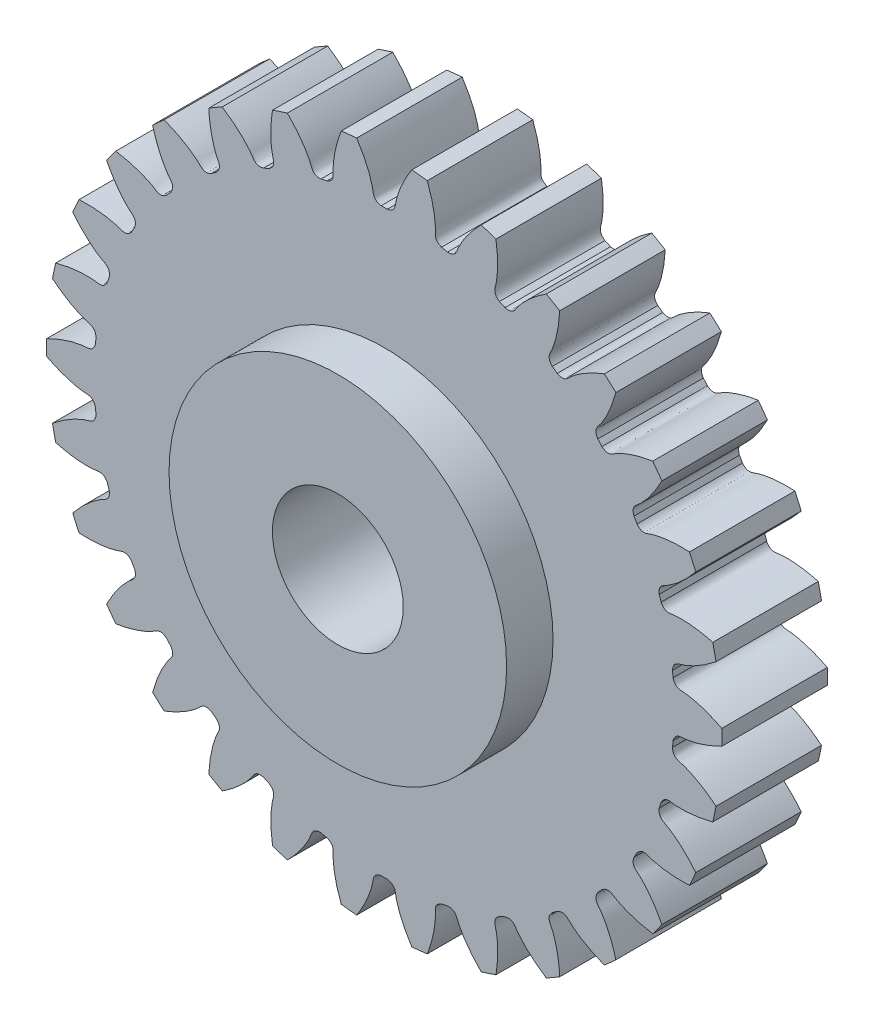
SolidWorks part; units mm, degrees
ref_plane "前视基准面" through (0, 0, 0) normal (0, 0, 1) x (1, 0, 0)
ref_plane "上视基准面" through (0, 0, 0) normal (0, 1, 0) x (1, 0, 0)
ref_plane "右视基准面" through (0, 0, 0) normal (1, 0, 0) x (0, 0, -1)
sketch "草图1" plane through (0, 0, 0) normal (0, 0, 1) x (1, 0, 0)
  circle A0 centre (0, 0) radius 8
extrude "凸台-拉伸1" add sketch "草图1" along normal blind 2.5
ref_axis "基准轴1" through (0, 0, -0.15) along (0, 0, 1)
sketch "草图2" plane through (0, 0, 0) normal (0, 0, 1) x (1, 0, 0)
  line L0 (0, 0) -> (0, 8) construction
  circle A0 centre (0, 0) radius 8 construction
  arc A1 (0.0728, 6.8746) -> (-0.0728, 6.8746) centre (0, 0) ccw
  arc A2 (1.6832, 9.0953) -> (-1.6832, 9.0953) centre (0, 0) ccw
  spline S0 degree 3 poles (0.0728, 6.8746) (0.2541, 6.9065) (0.2552, 7.0236) (0.2795, 7.1443) (0.285, 7.1691) (0.2916, 7.1965) (0.2995, 7.2264) (0.3088, 7.259) (0.3196, 7.294) (0.3319, 7.3315) (0.3459, 7.3714) (0.3617, 7.4137) (0.3794, 7.4582) (0.3991, 7.505) (0.4208, 7.554) (0.4447, 7.605) (0.4709, 7.6581) (0.4994, 7.7132) (0.5303, 7.7702) (0.5638, 7.829) (0.5999, 7.8895) (0.6387, 7.9517) (0.6803, 8.0155) (0.7247, 8.0807) (0.772, 8.1474) (0.8224, 8.2154) (0.8758, 8.2845) (0.9324, 8.3548) (0.9921, 8.4261) (1.0552, 8.4983) (1.1215, 8.5713) (1.1913, 8.6451) (1.2645, 8.7194) (1.3411, 8.7942) (1.4213, 8.8694) (1.5345, 8.9713) (1.6227, 9.046) (1.6832, 9.0953) knots 0 0 0 0 0.115324 0.123413 0.132512 0.142623 0.153745 0.165878 0.179022 0.193177 0.208343 0.22452 0.241708 0.259907 0.279117 0.299338 0.320571 0.342814 0.366068 0.390334 0.41561 0.441898 0.469196 0.497506 0.526827 0.557158 0.588501 0.620855 0.65422 0.688595 0.723982 0.76038 0.797789 0.836209 0.87564 0.916083 1 1 1 1
  spline S1 degree 3 poles (-0.0728, 6.8746) (-0.2541, 6.9065) (-0.2552, 7.0236) (-0.2795, 7.1443) (-0.285, 7.1691) (-0.2916, 7.1965) (-0.2995, 7.2264) (-0.3088, 7.259) (-0.3196, 7.294) (-0.3319, 7.3315) (-0.3459, 7.3714) (-0.3617, 7.4137) (-0.3794, 7.4582) (-0.3991, 7.505) (-0.4208, 7.554) (-0.4447, 7.605) (-0.4709, 7.6581) (-0.4994, 7.7132) (-0.5303, 7.7702) (-0.5638, 7.829) (-0.5999, 7.8895) (-0.6387, 7.9517) (-0.6803, 8.0155) (-0.7247, 8.0807) (-0.772, 8.1474) (-0.8224, 8.2154) (-0.8758, 8.2845) (-0.9324, 8.3548) (-0.9921, 8.4261) (-1.0552, 8.4983) (-1.1215, 8.5713) (-1.1913, 8.6451) (-1.2645, 8.7194) (-1.3411, 8.7942) (-1.4213, 8.8694) (-1.5345, 8.9713) (-1.6227, 9.046) (-1.6832, 9.0953) knots 0 0 0 0 0.115324 0.123413 0.132512 0.142623 0.153745 0.165878 0.179022 0.193177 0.208343 0.22452 0.241708 0.259907 0.279117 0.299338 0.320571 0.342814 0.366068 0.390334 0.41561 0.441898 0.469196 0.497506 0.526827 0.557158 0.588501 0.620855 0.65422 0.688595 0.723982 0.76038 0.797789 0.836209 0.87564 0.916083 1 1 1 1
extrude "切除-拉伸1" cut sketch "草图2" along normal through all
pattern_circular "阵列(圆周)1" count 30 every 12 about axis through (0, 0, -0.15) along (0, 0, 1) of "切除-拉伸1"
sketch "草图3" plane through (0, 0, 0) normal (0, 0, 1) x (1, 0, 0)
  circle A0 centre (0, 0) radius 7.5 construction
  dimension "Dn" = 15
sketch "草图6" plane through (0, 0, 2.5) normal (0, 0, 1) x (1, 0, 0)
  circle A0 centre (0, 0) radius 4
  dimension "D1" = 8
extrude "凸台-拉伸3" add sketch "草图6" along normal blind 1.1
sketch "草图4" plane through (0, 0, 0) normal (0, 0, -1) x (-1, 0, 0)
  line L0 (0, 0) -> (0, 0.5383) construction
  arc A0 (-0.775, 1.3423) -> (0.775, 1.3423) centre (0, 0) ccw
  arc A1 (-0.775, 1.3423) -> (0.775, 1.3423) centre (0, 0) cw
  dimension "D1" = 3.1
extrude "切除-拉伸2" cut sketch "草图4" along normal up to next from surface starting at face at (4, 0, 3.6)
